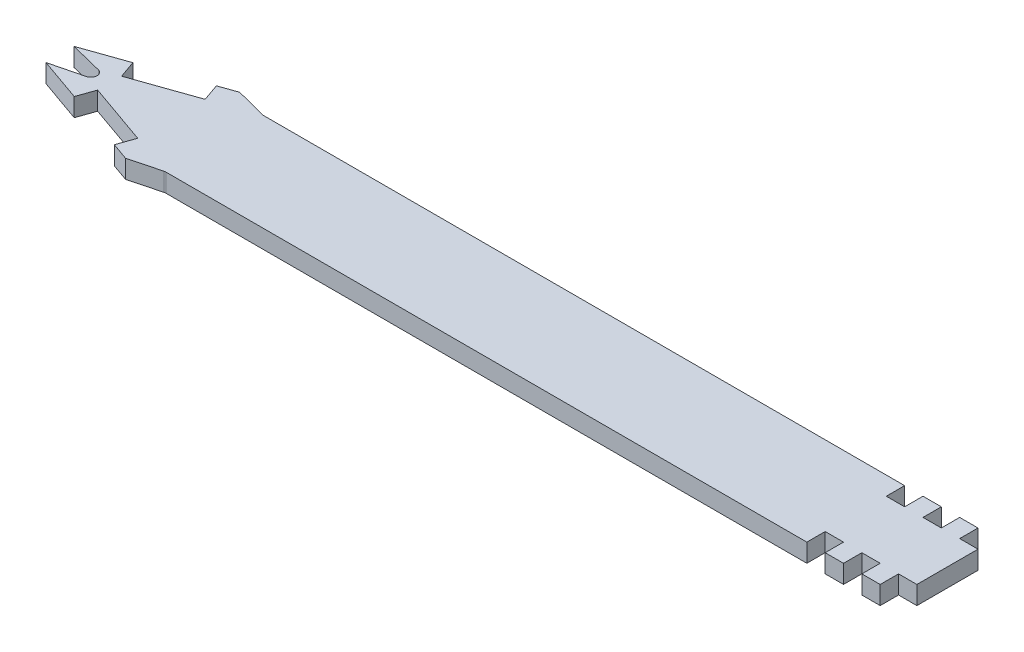
SolidWorks part; units mm, degrees
ref_plane "Front Plane" through (0, 0, 0) normal (0, 0, 1) x (1, 0, 0)
ref_plane "Top Plane" through (0, 0, 0) normal (0, 1, 0) x (1, 0, 0)
ref_plane "Right Plane" through (0, 0, 0) normal (1, 0, 0) x (0, 0, -1)
sketch "Sketch1" plane through (0, 0, 0) normal (0, 1, 0) x (1, 0, 0)
  line L0 (-450, 300) -> (-400, 300)
  line L1 (-400, 300) -> (-200, 250)
  line L2 (-200, 250) -> (200, 250) construction
  line L3 (200, 250) -> (600, 40) construction
  line L4 (600, 40) -> (1200, 40)
  line L5 (-450, -300) -> (-400, -300)
  line L6 (-400, -300) -> (-200, -250)
  line L7 (-200, -250) -> (200, -250) construction
  line L8 (200, -250) -> (600, -40) construction
  line L9 (600, -40) -> (1200, -40)
  line L10 (600, 40) -> (600, -40) construction
  line L11 (200, -250) -> (200, 250) construction
  line L12 (-200, 250) -> (-200, -250) construction
  line L13 (-400, -300) -> (-400, 300) construction
  line L14 (0, 0) -> (200, 0) construction
  line L15 (0, 250) -> (0, 0) construction
  line L16 (1200, 40) -> (1200, -40)
  line L17 (-450, 300) -> (-450, -300)
  line L18 (600, 0) -> (200, 0) construction
  line L19 (-450, 0) -> (-400, 0) construction
  line L20 (-400, 0) -> (-200, 0) construction
  line L21 (-200, 0) -> (0, 0) construction
  line L22 (-200, 250) -> (600, 40)
  line L23 (600, -40) -> (-200, -250)
  dimension "D1" = 600
  dimension "D2" = 200
  dimension "D3" = 50
  dimension "D4" = 400
  dimension "D5" = 500
  dimension "D6" = 80
  dimension "D7" = 600
  dimension "D8" = 400
extrude "Boss-Extrude1" add sketch "Sketch1" along normal blind 15
sketch "Sketch2" plane through (0, 0, 0) normal (0, 0, 1) x (1, 0, 0)
  line L0 (-450, 0) -> (-450, -40)
  line L1 (-450, -40) -> (-400, -40)
  line L2 (-400, -40) -> (-400, 0)
  line L3 (-400, 0) -> (-200, 0) construction
  line L4 (-400, 0) -> (-450, 0)
  line L5 (-440, -15) -> (-440, -40)
  line L6 (-410, -15) -> (-410, -40)
  line L7 (-425, 0) -> (-425, -15) construction
  circle A0 centre (-425, -15) radius 15
  dimension "D1" = 30
  dimension "D2" = 40
extrude "Boss-Extrude2" add sketch "Sketch2" along normal up to surface and the other way up to surface contours L4 L7 A0 L6 L1 L2 | L7 L4 L0 L1 L5 A0 up to face at (-425, 7.5, 300) other way up to face at (-425, 7.5, -300)
sketch "Sketch4" plane through (0, 0, 0) normal (0, 1, 0) x (1, 0, 0)
  line L0 (-450, 230) -> (-400, 230)
  line L1 (-450, 300) -> (-450, -300) construction
  line L2 (-400, 230) -> (-150, 167.5)
  line L3 (-150, 167.5) -> (-150, -167.5)
  line L4 (-150, -167.5) -> (-400, -230)
  line L5 (-400, -230) -> (-450, -230)
  line L6 (-400, 230) -> (-400, -230) construction
  line L7 (-200, 250) -> (-200, -250) construction
  line L9 (-200, 0) -> (-150, 0) construction
  line L10 (-400, -230) -> (-400, -300) construction
  line L11 (-400, -300) -> (-200, -250) construction
  line L12 (-450, 230) -> (-450, -230)
  line L14 (-200, 250) -> (-400, 300) construction
  line L15 (-100, 155) -> (-100, -155)
  line L16 (-100, -155) -> (520, 0)
  line L17 (520, 0) -> (-100, 155)
  line L18 (520, 0) -> (-100, 0) construction
  dimension "D1" = 460
  dimension "D2" = 300
  dimension "D3" = 50
extrude "Cut-Extrude2" cut sketch "Sketch4" against normal through all both and the other way through all
sketch "Sketch5" plane through (0, 0, 0) normal (1, 0, 0) x (0, 0, -1)
  line L0 (-300, 0) -> (-230, 0) construction
  line L1 (-285, 0) -> (-245, 0)
  line L2 (-285, 0) -> (-285, -40)
  line L3 (-285, -40) -> (-245, -40)
  line L4 (-245, 0) -> (-245, -40)
  line L5 (-300, -40) -> (-230, -40) construction
  line L6 (230, 0) -> (300, 0) construction
  line L7 (245, 0) -> (285, 0)
  line L8 (245, 0) -> (245, -40)
  line L9 (245, -40) -> (285, -40)
  line L10 (285, 0) -> (285, -40)
  line L11 (230, -40) -> (300, -40) construction
  line L12 (-300, 0) -> (-300, -40) construction
  line L13 (230, -40) -> (230, 0) construction
  line L14 (300, 0) -> (300, -40) construction
  dimension "D1" = 15
  dimension "D2" = 15
  dimension "D3" = 15
  dimension "D4" = 15
extrude "Cut-Extrude3" cut sketch "Sketch5" against normal through all
sketch "Sketch7" plane through (1200, 0, 0) normal (1, 0, 0) x (0, 0, -1)
  line L1 (-40, 15) -> (-87.5, 50)
  line L2 (-87.5, 50) -> (-87.5, 88.7)
  line L3 (-87.5, 88.7) -> (87.5, 88.7)
  line L4 (87.5, 88.7) -> (87.5, 50)
  line L5 (87.5, 50) -> (40, 15)
  line L7 (-40, 15) -> (40, 15)
  line L8 (-20, 50) -> (-20, 88.7)
  line L9 (87.5, 50) -> (-87.5, 50) construction
  line L10 (0, 88.7) -> (0, 50) construction
  line L11 (-20, 88.7) -> (20, 88.7)
  line L12 (0, 50) -> (0, 0) construction
  line L13 (20, 88.7) -> (20, 50)
  line L14 (-73, 88.7) -> (-63, 88.7)
  line L15 (-73, 88.7) -> (-73, 63.2)
  line L16 (-73, 63.2) -> (-63, 63.2)
  line L17 (-63, 88.7) -> (-63, 63.2)
  line L18 (48.5, 88.7) -> (58.5, 88.7)
  line L19 (48.5, 88.7) -> (48.5, 63.2)
  line L20 (48.5, 63.2) -> (58.5, 63.2)
  line L21 (58.5, 88.7) -> (58.5, 63.2)
  circle A0 centre (0, 50) radius 20
  dimension "D3" = 40
  dimension "D1" = 175
  dimension "D2" = 50
  dimension "D4" = 25.5
  dimension "D5" = 10
  dimension "D6" = 63
  dimension "D7" = 48.5
  dimension "D8" = 38.7
extrude "Boss-Extrude4" add sketch "Sketch7" against normal blind 75
sketch "Sketch8" plane through (0, 0, 0) normal (0, 0, 1) x (1, 0, 0)
  line L0 (1125, 88.7) -> (1200, 88.7) construction
  line L1 (1140, 88.7) -> (1185, 88.7)
  line L2 (1140, 88.7) -> (1140, 15)
  line L3 (1140, 15) -> (1185, 15)
  line L4 (1185, 88.7) -> (1185, 15)
  line L5 (1125, 15) -> (1200, 15) construction
  line L6 (1125, 50) -> (1125, 88.7) construction
  line L7 (1200, 50) -> (1200, 88.7) construction
  line L8 (1155, 88.7) -> (1170, 88.7) construction
  line L9 (1155, 88.7) -> (1170, 88.7)
  line L10 (1155, 88.7) -> (1155, 15)
  line L11 (1155, 15) -> (1170, 15)
  line L12 (1170, 88.7) -> (1170, 15)
  line L15 (1162.5, 50) -> (1162.5, 88.7) construction
  line L16 (1125, 50) -> (1200, 50) construction
  line L17 (1155, 88.7) -> (1170, 88.7) construction
  dimension "D1" = 15
  dimension "D2" = 15
  dimension "D3" = 15
extrude "Cut-Extrude4" cut sketch "Sketch8" against normal through all both and the other way through all contours L10 L1 L2 L3 | L1 L12 L3 L4
fillet "Fillet1" radius 5 53 edges at (1192.5, 50, 87.5) (1162.5, 50, 87.5) (1132.5, 50, 87.5) (1192.5, 50, -87.5) (1162.5, 50, -87.5) (1132.5, 50, -87.5) (1192.5, 88.7, -87.5) (1162.5, 88.7, -87.5) (1132.5, 88.7, -87.5) (1132.5, 88.7, -58.5) (1162.5, 88.7, -58.5) (1192.5, 88.7, -58.5) (1192.5, 88.7, -48.5) (1162.5, 88.7, -48.5) (1132.5, 88.7, -48.5) (1192.5, 88.7, -20) (1162.5, 88.7, -20) (1132.5, 88.7, -20) (1192.5, 88.7, 63) (1162.5, 88.7, 63) (1132.5, 88.7, 63) (1132.5, 88.7, 87.5) (1162.5, 88.7, 87.5) (1192.5, 88.7, 87.5) (1192.5, 88.7, 73) (1162.5, 88.7, 73) (1132.5, 88.7, 73) (1192.5, 88.7, 20) (1162.5, 88.7, 20) (1132.5, 88.7, 20) (600, 7.5, 40) (600, 7.5, -40) (520, 7.5, 0) (-440, -40, -292.5) (-440, -40, -237.5) (-400, -40, -292.5) (-400, -40, -237.5) (-450, -40, -237.5) (-410, -40, -237.5) (-450, -40, -292.5) (-410, -40, -292.5) (-150, 7.5, 167.5) (-100, 7.5, 155) (-150, 7.5, -167.5) (-100, 7.5, -155) (-450, -40, 237.5) (-410, -40, 237.5) (-440, -40, 237.5) (-400, -40, 237.5) (-450, -40, 292.5) (-440, -40, 292.5) (-400, -40, 292.5) (-410, -40, 292.5)
sketch "Sketch9" plane through (0, 0, 0) normal (0, 1, 0) x (1, 0, 0)
  line L35 (-450, -300) -> (-400, -300) construction
  line L36 (-425, -300) -> (-425, -285) construction
  line L37 (-450, 0) -> (0, 0) construction
  line L38 (-437.5, -300) -> (-412.5, -300)
  line L39 (-437.5, -300) -> (-437.5, -285)
  line L56 (1140, -40) -> (1140, -85.466) construction
  line L57 (1200, -40) -> (1185, -40)
  line L58 (1200, -40) -> (1200, -25)
  line L59 (1200, -25) -> (1185, -25)
  line L60 (1185, -40) -> (1185, -25)
  line L61 (1200, 40) -> (1185, 40)
  line L62 (1200, 40) -> (1200, 25)
  line L63 (1200, 25) -> (1185, 25)
  line L64 (1185, 40) -> (1185, 25)
  line L65 (1170, 40) -> (1155, 40)
  line L66 (1170, 40) -> (1170, 25)
  line L67 (1170, 25) -> (1155, 25)
  line L68 (1155, 40) -> (1155, 25)
  line L69 (1140, 40) -> (1125, 40)
  line L70 (1140, 40) -> (1140, 25)
  line L71 (1140, 25) -> (1125, 25)
  line L72 (1125, 40) -> (1125, 25)
  line L73 (1125, -40) -> (1140, -40)
  line L74 (1125, -40) -> (1125, -25)
  line L75 (1125, -25) -> (1140, -25)
  line L76 (1140, -40) -> (1140, -25)
  line L77 (1155, -40) -> (1170, -40)
  line L78 (1155, -40) -> (1155, -25)
  line L79 (1155, -25) -> (1170, -25)
  line L80 (1170, -40) -> (1170, -25)
  line L81 (600.6453, -40) -> (1200, -40) construction
  line L82 (1200, 40) -> (600.6453, 40) construction
  line L83 (1140, 40) -> (1125, 40) construction
  line L84 (1125, 85.466) -> (1125, 40) construction
  line L85 (1140, -25) -> (1155, -25) construction
  line L86 (1170, -25) -> (1185, -25) construction
  line L87 (1185, 25) -> (1170, 25) construction
  line L88 (1155, 25) -> (1140, 25) construction
  line L89 (-437.5, -285) -> (-412.5, -285)
  line L90 (-412.5, -300) -> (-412.5, -285)
  line L92 (-410, -230) -> (-440, -230) construction
  line L93 (-437.5, -230) -> (-412.5, -230)
  line L94 (-437.5, -230) -> (-437.5, -245)
  line L95 (-437.5, -245) -> (-412.5, -245)
  line L96 (-412.5, -230) -> (-412.5, -245)
  line L97 (-425, -245) -> (-400, -245) construction
  line L98 (-425, -285) -> (-425, -245) construction
  line L99 (-425, 285) -> (-425, 245) construction
  line L100 (-425, 300) -> (-425, 285) construction
  line L101 (-450, 300) -> (-400, 300) construction
  line L102 (-412.5, 230) -> (-412.5, 245)
  line L103 (-437.5, 245) -> (-412.5, 245)
  line L104 (-437.5, 230) -> (-437.5, 245)
  line L105 (-437.5, 230) -> (-412.5, 230)
  line L106 (-412.5, 300) -> (-412.5, 285)
  line L107 (-437.5, 285) -> (-412.5, 285)
  line L108 (-437.5, 300) -> (-437.5, 285)
  line L109 (-437.5, 300) -> (-412.5, 300)
  dimension "D1" = 15
  dimension "D2" = 25
  dimension "D3" = 15
extrude "Cut-Extrude5" cut sketch "Sketch9" against normal through all both and the other way through all
sketch "Sketch10" plane through (0, 0, 0) normal (0, 0, 1) x (1, 0, 0)
  line L1 (-450, 15) -> (1200, 15)
  line L2 (-450, 15) -> (-450, 0)
  line L3 (-450, 0) -> (1200, 0)
  line L4 (1200, 15) -> (1200, 0)
  line L5 (-450, 15) -> (-450, -35) construction
  line L6 (-486.0808, 110.0266) -> (1242.84, 110.0266)
  line L7 (-486.0808, 110.0266) -> (-486.0808, -68.8272)
  line L8 (-486.0808, -68.8272) -> (1242.84, -68.8272)
  line L9 (1242.84, 110.0266) -> (1242.84, -68.8272)
  dimension "D1" = 15
extrude "Cut-Extrude6" cut sketch "Sketch10" against normal through all both and the other way through all
sketch "Sketch11" plane through (0, 0, 0) normal (0, 1, 0) x (1, 0, 0)
  line L1 (-450, 300) -> (-437.5, 300) construction
  line L7 (-93.7873, -153.4468) -> (500.5971, -4.8507) construction
  line L8 (-200, -250) -> (599.3758, -40.1638) construction
  line L18 (-450, -300) -> (1200, -300)
  line L19 (-450, -300) -> (-450, 300)
  line L20 (-450, 300) -> (1200, 300)
  line L21 (1200, -300) -> (1200, 300)
  line L26 (574.4681, -46.7021) -> (600.6453, -40)
  line L27 (600.6453, -40) -> (500.5971, -4.8507)
  line L28 (500.5971, -4.8507) -> (474.1575, -11.4606)
  line L29 (574.4681, -46.7021) -> (474.1575, -11.4606)
  line L30 (560.3161, -41.7302) -> (565.288, -27.5782)
  line L31 (509.7772, -23.9747) -> (514.7492, -9.8227)
  line L32 (-253.7911, 0) -> (928.7767, 0) construction
  line L33 (509.7772, 23.9747) -> (514.7492, 9.8227)
  line L34 (560.3161, 41.7302) -> (565.288, 27.5782)
  line L35 (574.4681, 46.7021) -> (474.1575, 11.4606)
  line L36 (600.6453, 40) -> (500.5971, 4.8507)
  line L37 (600.6453, 40) -> (574.4681, 46.7021)
  line L38 (500.5971, 4.8507) -> (474.1575, 11.4606)
  line L39 (1200, 25) -> (1200, -25) construction
  line L40 (1200, -40) -> (600.6453, -40)
  line L41 (1200, -40) -> (1200, 40)
  line L42 (1200, 40) -> (600.6453, 40)
  line L43 (600.6453, -40) -> (600.6453, 40)
  point P0 (0, 0)
  dimension "D6" = 15
  dimension "D7" = 15
  dimension "D8" = 15
sketch "Sketch12" plane through (0, 0, 0) normal (0, 1, 0) x (1, 0, 0)
  line L0 (441.5362, 0) -> (600.6453, 55.8988)
  line L1 (-450, -300) -> (600.6453, -300)
  line L2 (-450, -300) -> (-450, 300)
  line L3 (-450, 300) -> (600.6453, 300)
  line L4 (600.6453, -300) -> (600.6453, 300)
  line L5 (-200253.7911, 0) -> (200928.7767, 0) construction
  line L6 (574.4681, 46.7021) -> (474.1575, 11.4606) construction
  line L7 (441.5362, 0) -> (600.6453, -55.8988)
  line L8 (574.4681, -46.7021) -> (474.1575, -11.4606) construction
  line L9 (600.6453, -40) -> (500.5971, -4.8507)
  line L10 (500.5971, -4.8507) -> (474.1575, -11.4606)
  line L11 (514.7492, -9.8227) -> (509.7772, -23.9747)
  line L12 (560.3161, -41.7302) -> (565.288, -27.5782)
  line L13 (600.6453, -40) -> (574.4681, -46.7021)
  line L14 (574.4681, 46.7021) -> (600.6453, 40)
  line L15 (600.6453, 40) -> (500.5971, 4.8507)
  line L16 (500.5971, 4.8507) -> (474.1575, 11.4606)
  line L17 (514.7492, 9.8227) -> (509.7772, 23.9747)
  line L18 (560.3161, 41.7302) -> (565.288, 27.5782)
extrude "Cut-Extrude8" cut sketch "Sketch12" along normal through all contours L7 L0 L4 L3 L2 L1 | L7 L12 L9 L11 | L18 L0 L17 L15
